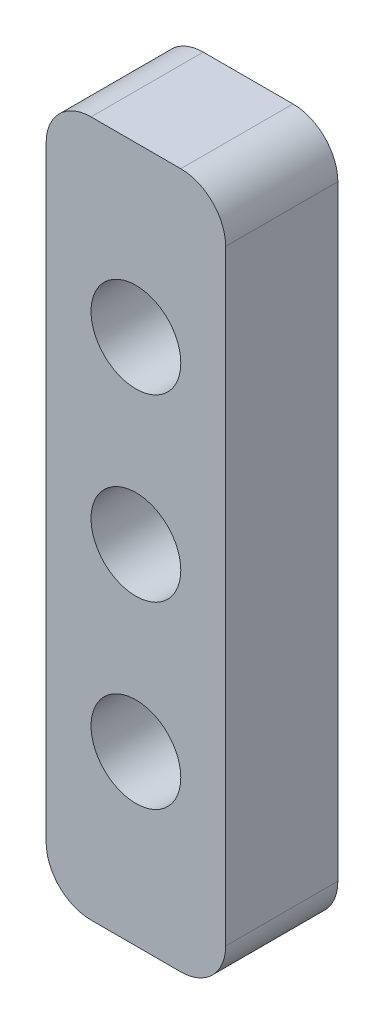
SolidWorks part; units mm, degrees
ref_plane "Front Plane" through (0, 0, 0) normal (0, 0, 1) x (1, 0, 0)
ref_plane "Top Plane" through (0, 0, 0) normal (0, 1, 0) x (1, 0, 0)
ref_plane "Right Plane" through (0, 0, 0) normal (1, 0, 0) x (0, 0, -1)
sketch "Sketch1" plane through (0, 0, 0) normal (0, 0, 1) x (1, 0, 0)
  line L0 (0, -13.5) -> (0, 13.5)
  line L1 (8, -13.5) -> (8, 13.5)
  line L2 (2, 15.5) -> (6, 15.5)
  line L3 (2, -15.5) -> (6, -15.5)
  line L4 (8, -14.5) -> (8, 14.5) construction
  line L5 (0, -14.5) -> (0, 14.5) construction
  arc A0 (8, 13.5) -> (6, 15.5) centre (6, 13.5) ccw
  arc A1 (0, 13.5) -> (2, 15.5) centre (2, 13.5) cw
  arc A2 (0, -13.5) -> (2, -15.5) centre (2, -13.5) ccw
  arc A3 (8, -13.5) -> (6, -15.5) centre (6, -13.5) cw
  point P4 (0, 0)
  point P13 (0, 15.5)
  dimension "D3" = 2
  dimension "D1" = 31
  dimension "D2" = 8
extrude "Boss-Extrude1" add sketch "Sketch1" along normal blind 5
sketch "Sketch3" plane through (0, 0, 5) normal (0, 0, 1) x (1, 0, 0)
  line L0 (0, 0) -> (10.5795, 0) construction
  line L1 (4, 15.5) -> (4, -16.6132) construction
  line L2 (6, 15.5) -> (2, 15.5) construction
  circle A0 centre (4, 0) radius 2
  circle A1 centre (4, 8) radius 2
  circle A2 centre (4, -8) radius 2
  dimension "D1" = 4
  dimension "D2" = 4
  dimension "D3" = 4
  dimension "D4" = 8
  dimension "D5" = 8
extrude "Cut-Extrude2" cut sketch "Sketch3" against normal through all
